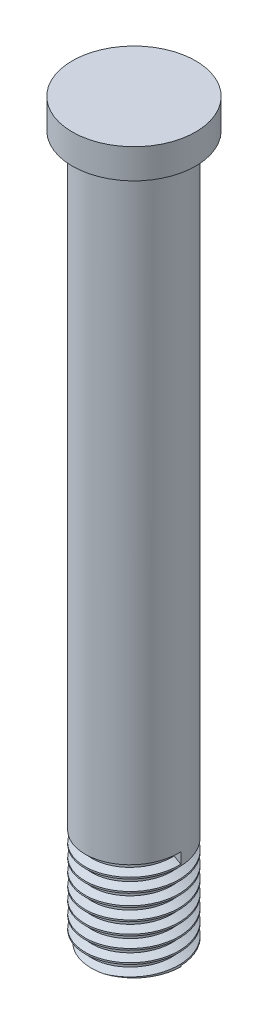
SolidWorks part; units mm, degrees
ref_plane "Front Plane" through (0, 0, 0) normal (0, 0, 1) x (1, 0, 0)
ref_plane "Top Plane" through (0, 0, 0) normal (0, 1, 0) x (1, 0, 0)
ref_plane "Right Plane" through (0, 0, 0) normal (1, 0, 0) x (0, 0, -1)
sketch "Sketch1" plane through (0, 0, 0) normal (0, 1, 0) x (1, 0, 0)
  circle A0 centre (0, 0) radius 4.75
  dimension "D1" = 9.5
extrude "Boss-Extrude1" add sketch "Sketch1" along normal blind 71
sketch "Sketch2" plane through (0, 71, 0) normal (0, 1, 0) x (1, 0, 0)
  circle A0 centre (0, 0) radius 6.25
  circle A1 centre (0, 0) radius 4.75 construction
  dimension "D1" = 1.5
extrude "Boss-Extrude2" add sketch "Sketch2" along normal blind 3
thread "Thread1" pitch 1.25 method cut profile "Thread Profile1" start angle 0, offset 1, length 10, pitch 1.25, diameter 9.5
ref_plane "Plane1" through (4.75, -1, 0) normal (0, 0, 1) x (1, 0, 0)
sketch "Thread Profile1" plane through (4.75, -1, 0) normal (0, 0, 1) x (1, 0, 0)
  line L0 (0, 0) -> (0, 1.25) construction
  line L11 (0, 0) -> (0, 1.0937)
  line L12 (0, 1.0937) -> (-0.6766, 0.7031)
  line L13 (-0.6766, 0.7031) -> (-0.6766, 0.3906)
  line L15 (-0.6766, 0.3906) -> (0, 0)
  line L17 (-0.6766, 0.5469) -> (0, 0.5469) construction
  point P2 (0, 0)
  dimension "Pitch" = 1.25
  dimension "Profile_Angle" = 60
  dimension "Profile_Land" = 0.3125
  dimension "Profile_Height" = 0.6766
